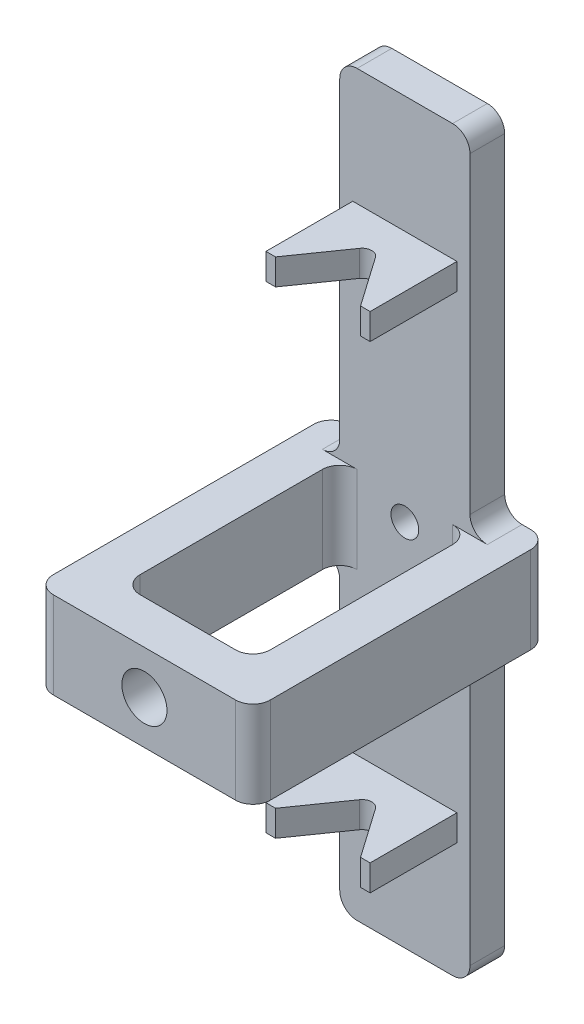
SolidWorks part; units mm, degrees
ref_plane "Front Plane" through (0, 0, 0) normal (0, 0, 1) x (1, 0, 0)
ref_plane "Top Plane" through (0, 0, 0) normal (0, 1, 0) x (1, 0, 0)
ref_plane "Right Plane" through (0, 0, 0) normal (1, 0, 0) x (0, 0, -1)
sketch "Sketch1" plane through (0, 0, 0) normal (0, 0, 1) x (1, 0, 0)
  line L1 (-7.5, 42.5) -> (7.5, 42.5)
  line L2 (-7.5, 42.5) -> (-7.5, -42.5)
  line L3 (-7.5, -42.5) -> (7.5, -42.5)
  line L4 (7.5, 42.5) -> (7.5, -42.5)
  line L5 (-7.5, 42.5) -> (7.5, -42.5) construction
  line L6 (-7.5, -42.5) -> (7.5, 42.5) construction
  point P0 (0, 0)
  dimension "D1" = 85
  dimension "D2" = 15
extrude "Boss-Extrude1" add sketch "Sketch1" along normal blind 4
sketch "Sketch2" plane through (0, 0, 4) normal (0, 0, 1) x (1, 0, 0)
  line L0 (0, 42.5) -> (0, 27.5)
  line L1 (0, -42.5) -> (0, -27.5)
  line L3 (-6, 29) -> (6, 29)
  line L4 (7.5, -42.5) -> (7.5, 42.5)
  line L5 (7.5, 42.5) -> (-7.5, 42.5)
  line L6 (-7.5, 42.5) -> (-7.5, -42.5)
  line L7 (-7.5, -42.5) -> (7.5, -42.5)
  line L9 (7.5, 42.5) -> (-7.5, 42.5)
  line L11 (-7.5, -42.5) -> (7.5, -42.5)
  line L12 (-6, 29) -> (-6, 26)
  line L13 (-6, 26) -> (6, 26)
  line L14 (6, 29) -> (6, 26)
  line L15 (-6, 29) -> (6, 26) construction
  line L16 (-6, 26) -> (6, 29) construction
  line L17 (-6, -29) -> (6, -29)
  line L18 (-6, -29) -> (-6, -26)
  line L19 (-6, -26) -> (6, -26)
  line L20 (6, -29) -> (6, -26)
  line L21 (-6, -29) -> (6, -26) construction
  line L22 (-6, -26) -> (6, -29) construction
  dimension "D2" = 15
  dimension "D3" = 15
  dimension "D4" = 3
  dimension "D5" = 12
  dimension "D6" = 3
  dimension "D7" = 12
  dimension "D1" = 0
extrude "Boss-Extrude2" add sketch "Sketch2" along normal blind 10 contours L14 L3 L12 L13 | L17 L20 L19 L18 region at (3, 28.8763, 4) region at (-3, -28.8763, 4)
sketch "Sketch3" plane through (0, 29, 0) normal (0, 1, 0) x (1, 0, 0)
  line L0 (0, -14) -> (0, -7)
  line L1 (-0.9046, -8.2934) -> (-4.896, -14)
  line L2 (0.9046, -8.2934) -> (4.896, -14)
  line L4 (6, -4) -> (-6, -4)
  line L5 (-6, -4) -> (-6, -14)
  line L6 (-6, -14) -> (6, -14)
  line L7 (6, -14) -> (6, -4)
  line L8 (6, -4) -> (-6, -4)
  line L9 (-6, -4) -> (-6, -12.896)
  line L10 (-4.896, -14) -> (4.896, -14)
  line L11 (6, -12.896) -> (6, -4)
  arc A0 (6, -12.896) -> (4.896, -14) centre (4.896, -12.896) cw
  arc A1 (-4.896, -14) -> (-6, -12.896) centre (-4.896, -12.896) cw
  arc A2 (0.9046, -8.2934) -> (-0.9046, -8.2934) centre (0, -8.9261) ccw
  line M9 (-6, -14) -> (6, -14)
  dimension "D2" = 1.104
  dimension "D4" = 1.104
  dimension "D3" = 7
  dimension "D1" = 0
extrude "Cut-Extrude1" cut sketch "Sketch3" against normal blind 60 contours L2 A2 L0 M9 | L0 A2 L1 M9 region at (-1.6555, 29, 11.7355) region at (1.6555, 29, 11.7355)
sketch "Sketch4" plane through (0, 0, 4) normal (0, 0, 1) x (1, 0, 0)
  line L0 (0, 0) -> (0, -15.4)
  circle A0 centre (0, -15.4) radius 1.6
  circle A1 centre (0, 0) radius 1.6
  dimension "D2" = 3.2
  dimension "D3" = 3.2
  dimension "D1" = 15.4
extrude "Cut-Extrude2" cut sketch "Sketch4" against normal blind 4 contours A1 | A0 region at (1.0994, -14.3006, 4) region at (-1.0994, 1.0994, 4)
sketch "Sketch5" plane through (0, 42.5, 0) normal (0, 1, 0) x (1, 0, 0)
  line L1 (7.5, 0) -> (12.5, 0)
  line L2 (7.5, 0) -> (7.5, -4)
  line L3 (7.5, -4) -> (12.5, -4)
  line L4 (12.5, 0) -> (12.5, -4)
  line L5 (-7.5, 0) -> (-12.5, 0)
  line L6 (-7.5, 0) -> (-7.5, -4)
  line L7 (-7.5, -4) -> (-12.5, -4)
  line L8 (-12.5, 0) -> (-12.5, -4)
  dimension "D1" = 5
  dimension "D2" = 5
  dimension "D3" = 4
  dimension "D4" = 4
extrude "Boss-Extrude3" add sketch "Sketch5" against normal blind 50
sketch "Sketch8" plane through (0, 0, 4) normal (0, 0, 1) x (1, 0, 0)
  line L1 (12.5, 42.5) -> (7.5, 42.5)
  line L2 (12.5, 42.5) -> (12.5, 2.5)
  line L3 (12.5, 2.5) -> (7.5, 2.5)
  line L4 (7.5, 42.5) -> (7.5, 2.5)
  line L5 (-12.5, 42.5) -> (-7.5, 42.5)
  line L6 (-12.5, 42.5) -> (-12.5, 2.5)
  line L7 (-12.5, 2.5) -> (-7.5, 2.5)
  line L8 (-7.5, 42.5) -> (-7.5, 2.5)
  dimension "D1" = 40
  dimension "D2" = 5
  dimension "D3" = 40
  dimension "D4" = 5
extrude "Cut-Extrude3" cut sketch "Sketch8" against normal blind 4
sketch "Sketch10" plane through (0, 0, 4) normal (0, 0, 1) x (1, 0, 0)
  line L1 (12.5, 2.5) -> (7.5, 2.5)
  line L2 (12.5, 2.5) -> (12.5, -7.5)
  line L3 (12.5, -7.5) -> (7.5, -7.5)
  line L4 (7.5, 2.5) -> (7.5, -7.5)
  line L5 (-12.5, 2.5) -> (-7.5, 2.5)
  line L6 (-12.5, 2.5) -> (-12.5, -7.5)
  line L7 (-12.5, -7.5) -> (-7.5, -7.5)
  line L8 (-7.5, 2.5) -> (-7.5, -7.5)
extrude "Boss-Extrude4" add sketch "Sketch10" along normal blind 30
sketch "Sketch11" plane through (7.5, 0, 0) normal (-1, 0, 0) x (0, 0, 1)
  line L1 (34, 2.5) -> (29, 2.5)
  line L2 (34, 2.5) -> (34, -7.5)
  line L3 (34, -7.5) -> (29, -7.5)
  line L4 (29, 2.5) -> (29, -7.5)
  dimension "D1" = 10
  dimension "D2" = 5
extrude "Boss-Extrude5" add sketch "Sketch11" along normal up to surface (15 mm away) up to face at (-7.5, -2.5, 19)
fillet "Fillet2" radius 2 14 edges at (7.5, -42.5, 2) (-7.5, -42.5, 2) (-7.5, 42.5, 2) (7.5, 42.5, 2) (-7.5, -2.5, 29) (7.5, -2.5, 29) (12.5, -2.5, 34) (-12.5, -2.5, 34) (-12.5, -2.5, 0) (-7.5, 2.5, 2) (-7.5, -7.5, 2) (7.5, -7.5, 2) (7.5, 2.5, 2) (12.5, -2.5, 0)
sketch "Sketch12" plane through (0, 0, 34) normal (0, 0, 1) x (1, 0, 0)
  line L0 (-10.5, 2.5) -> (10.5, -7.5)
  line L1 (10.5, 2.5) -> (-10.5, -7.5)
  circle A0 centre (0, -2.5) radius 2.6
  dimension "D1" = 5.2
extrude "Cut-Extrude4" cut sketch "Sketch12" against normal blind 30 contours L1 A0 L0 | L0 A0 L1 | L1 A0 L0 | L0 A0 L1 region at (0, -1.1106, 34) region at (-1.6768, -2.5, 34) region at (1.6768, -2.5, 34) region at (0, -3.8894, 34)
fillet "Fillet3" radius 2 2 edges at (7.5, -2.5, 4) (-7.5, -2.5, 4)
